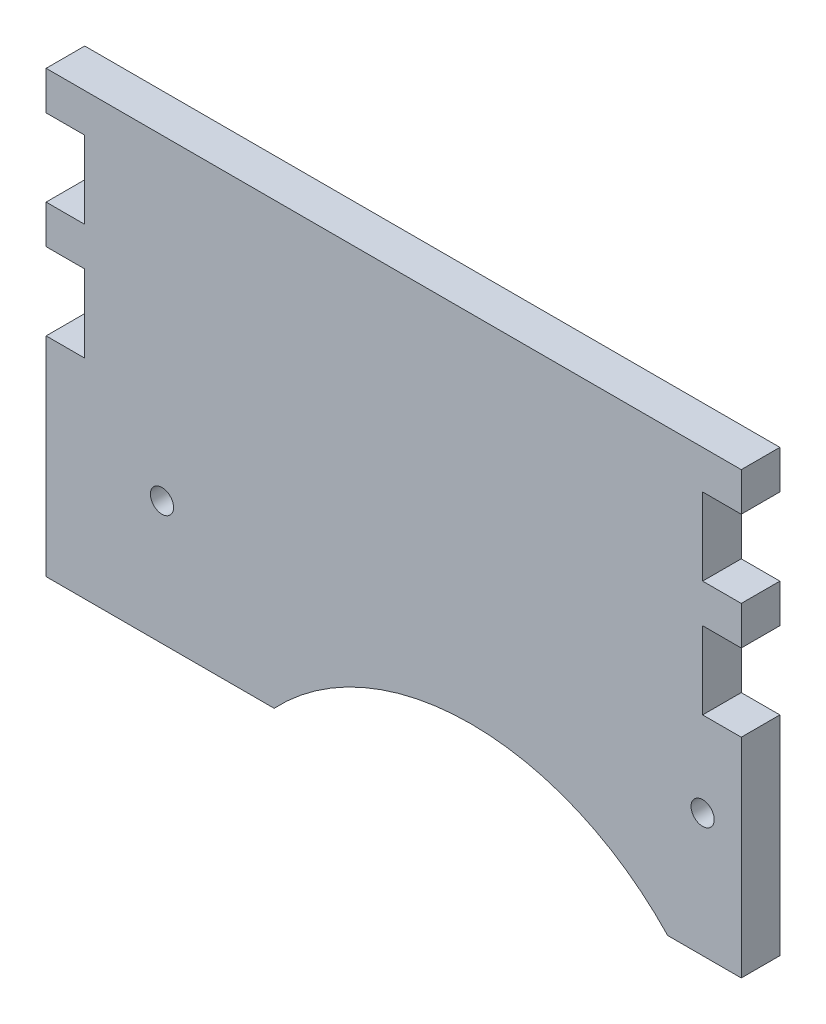
SolidWorks part; units mm, degrees
ref_plane "Plan de face" through (0, 0, 0) normal (0, 0, 1) x (1, 0, 0)
ref_plane "Plan de dessus" through (0, 0, 0) normal (0, 1, 0) x (1, 0, 0)
ref_plane "Plan de droite" through (0, 0, 0) normal (1, 0, 0) x (0, 0, -1)
sketch "Esquisse1" plane through (0, 0, 0) normal (0, 0, 1) x (1, 0, 0)
  line L0 (15, 67) -> (15, -4) construction
  line L1 (0, 0) -> (29.5245, 0)
  line L2 (0, 0) -> (0, 27)
  line L3 (0, 57) -> (90, 57)
  line L4 (90, 0) -> (90, 27)
  line L5 (0, 52) -> (0, 57)
  line L6 (85, 52) -> (90, 52)
  line L7 (85, 52) -> (85, 42)
  line L8 (85, 42) -> (90, 42)
  line L9 (90, 52) -> (90, 57)
  line L10 (15, 16) -> (85, 16) construction
  line L11 (80.4755, 0) -> (90, 0)
  line L12 (85, 37) -> (90, 37)
  line L13 (85, 37) -> (85, 27)
  line L14 (85, 27) -> (90, 27)
  line L16 (0, 52) -> (5, 52)
  line L17 (0, 37) -> (0, 42)
  line L18 (0, 42) -> (5, 42)
  line L19 (5, 52) -> (5, 42)
  line L20 (0, 37) -> (5, 37)
  line L21 (90, 37) -> (90, 42)
  line L22 (0, 27) -> (5, 27)
  line L23 (5, 37) -> (5, 27)
  circle A4 centre (15, 16) radius 1.5
  circle A5 centre (15, 16) radius 1.5 construction
  circle A6 centre (85, 16) radius 1.5
  circle A7 centre (55, -24) radius 35 construction
  arc A8 (29.5245, 0) -> (80.4755, 0) centre (55, -24) cw
  dimension "D8" = 10
  dimension "D9" = 3
  dimension "D10" = 70
  dimension "D13" = 70
  dimension "D2" = 15
  dimension "D3" = 41
  dimension "D4" = 16
  dimension "D5" = 90
  dimension "D7" = 5
  dimension "D11" = 5
  dimension "D12" = 5
  dimension "D14" = 40
  dimension "D15" = 40
extrude "Boss.-Extru.1" add sketch "Esquisse1" along normal blind 5 contours L1 A8 L11 L4 A6 L14 L13 L12 L21 L8 L7 L6 L9 L3 L5 L16 L19 L18 L17 L20 L23 L22 L2 A4 region at (44.1293, 30.1083, 0)
